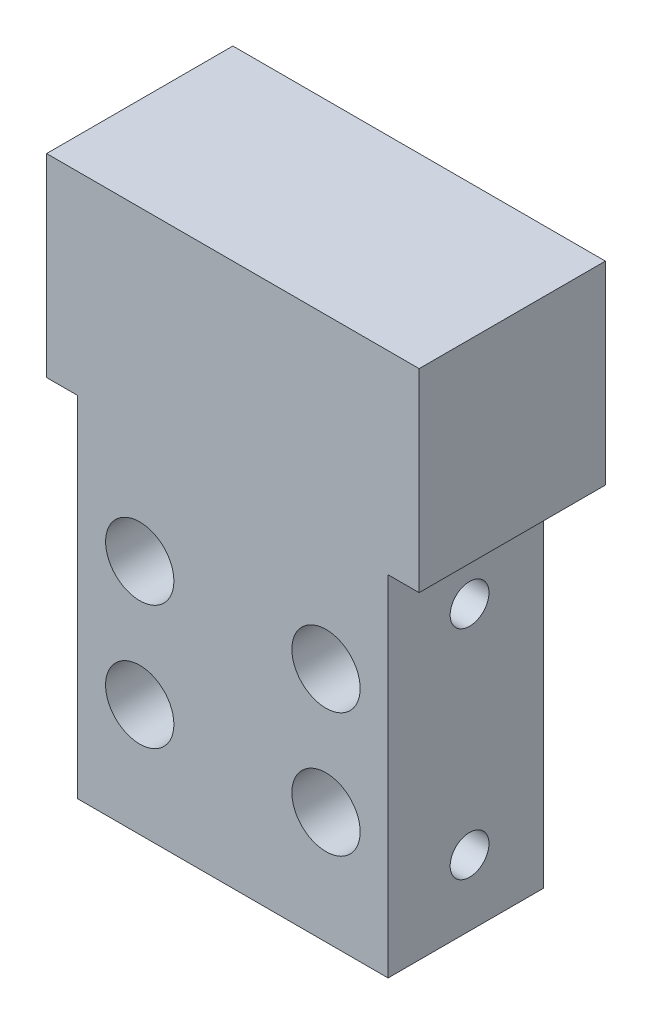
SolidWorks part; units mm, degrees
ref_plane "Front Plane" through (0, 0, 0) normal (0, 0, 1) x (1, 0, 0)
ref_plane "Top Plane" through (0, 0, 0) normal (0, 1, 0) x (1, 0, 0)
ref_plane "Right Plane" through (0, 0, 0) normal (1, 0, 0) x (0, 0, -1)
sketch "Sketch1" plane through (0, 0, 0) normal (0, 0, 1) x (1, 0, 0)
  line L1 (0, 0) -> (20, 0)
  line L2 (0, 0) -> (0, 22.5)
  line L3 (0, 22.5) -> (20, 22.5)
  line L4 (20, 0) -> (20, 22.5)
  dimension "D1" = 20
  dimension "D2" = 22.5
extrude "Boss-Extrude1" add sketch "Sketch1" along normal blind 10
hole_wizard "CBORE for M2 SHCS1" positions "Sketch2" profile "Sketch3" counterbore size "M2" standard "ANSI Metric" end condition through all
sketch "Sketch2" plane through (0, 0, 10) normal (0, 0, 1) x (1, 0, 0)
  line L0 (0, 22.5) -> (0, 0) construction
  line L1 (20, 22.5) -> (0, 22.5) construction
  point P0 (4, 15.25)
  point P11 (16, 15.25)
  point P12 (16, 7.25)
  point P13 (4, 7.25)
  point P20 (0, 0)
  dimension "D1" = 4
  dimension "D4" = 7.25
  dimension "D2" = 2
  dimension "D3" = 2
sketch "Sketch3" plane through (4, 15.25, 10) normal (1, 0, 0) x (0, -1, 0)
  line L0 (0, 0) -> (0, 10)
  line L1 (0, 10) -> (1.2, 10)
  line L3 (1.2, 10) -> (1.2, 7)
  line L4 (1.2, 7) -> (2.2, 7)
  line L5 (2.2, 7) -> (2.2, 0)
  line L7 (2.2, 0) -> (0, 0)
  line L11 (0, -6.35) -> (0, 107.95) construction
  dimension "Thru Hole Dia." = 2.4
  dimension "Thru Hole Depth" = 10
  dimension "C'Bore Dia." = 4.4
  dimension "C'Bore Depth" = 7
sketch "Sketch4" plane through (0, 22.5, 0) normal (0, 1, 0) x (1, 0, 0)
  line L0 (20, -10) -> (20, 0) construction
  line L1 (22, 2) -> (-2, 2)
  line L2 (22, 2) -> (22, -10)
  line L3 (22, -10) -> (-2, -10)
  line L4 (-2, 2) -> (-2, -10)
  line L5 (20, 0) -> (0, 0) construction
  line L6 (20, -10) -> (0, -10) construction
  point P5 (0, 0)
  dimension "D2" = 24
  dimension "D3" = 2
  dimension "D4" = 2
extrude "Boss-Extrude2" add sketch "Sketch4" along normal blind 12.5
hole_wizard "Tap Drill for M3x0.5 Tap1" positions "Sketch5" profile "Sketch6" hole size "M3x0.5" standard "ANSI Metric" end condition through all
sketch "Sketch5" plane through (20, 0, 0) normal (1, 0, 0) x (0, 0, -1)
  point P0 (-4.7518, 18.25)
  point P3 (-4.7518, 4.25)
sketch "Sketch6" plane through (20, 18.25, 4.7518) normal (0, 1, 0) x (0, 0, -1)
  line L0 (0, 0) -> (0, 22)
  line L1 (0, 22) -> (1.25, 22)
  line L2 (1.25, 22) -> (1.25, 0)
  line L5 (1.25, 0) -> (0, 0)
  line L11 (0, -6.35) -> (0, 107.95) construction
  dimension "Thru Hole Dia." = 2.5
  dimension "Thru Hole Depth" = 22
